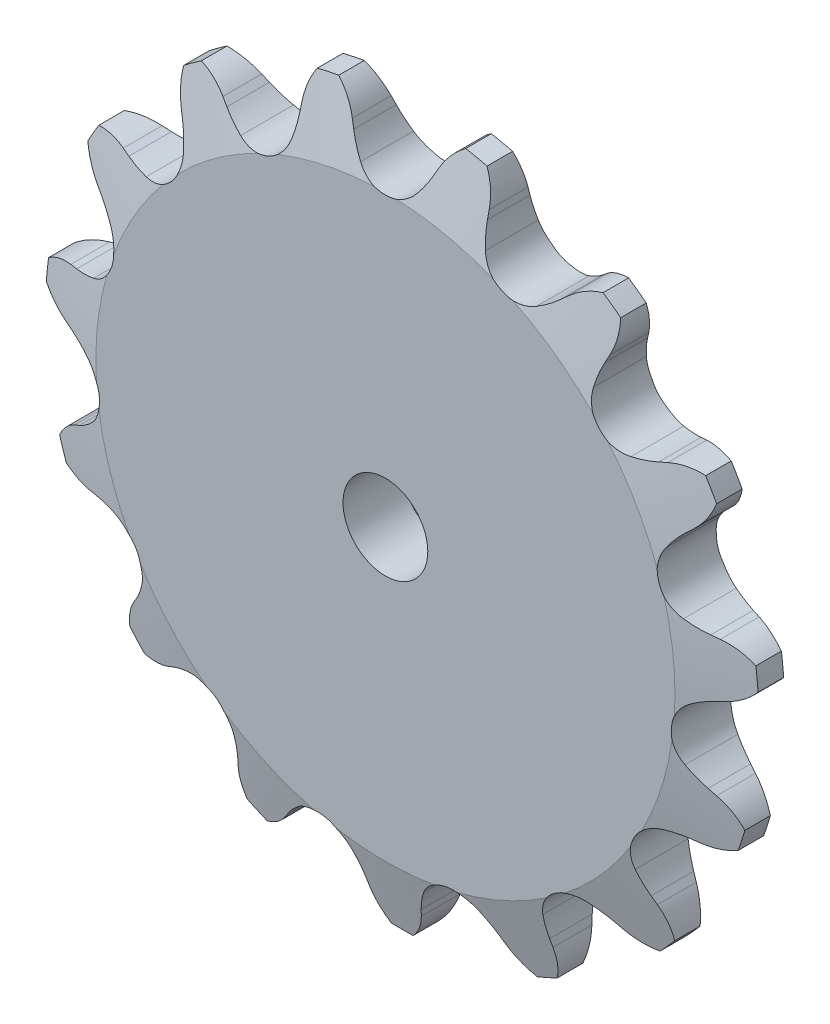
SolidWorks part; units mm, degrees
ref_plane "Front Plane" through (0, 0, 0) normal (0, 0, 1) x (1, 0, 0)
ref_plane "Top Plane" through (0, 0, 0) normal (0, 1, 0) x (1, 0, 0)
ref_plane "Right Plane" through (0, 0, 0) normal (1, 0, 0) x (0, 0, -1)
ref_axis "Axis1" through (0, 0, -88.99) along (0, 0, 1)
sketch "Sprocket-BaseSketch" plane through (0, 0, 0) normal (1, 0, 0) x (0, 0, -1)
  line L0 (1.397, 0) -> (1.397, 13.6672)
  line L1 (1.397, 13.6672) -> (0.6032, 16.8422)
  line L2 (0.6032, 16.8422) -> (-0.6032, 16.8422)
  line L3 (-0.6032, 16.8422) -> (-1.397, 13.6672)
  line L4 (-1.397, 13.6672) -> (-1.397, 0)
  line L5 (-1.397, 0) -> (1.397, 0)
  line L6 (5.588, 0) -> (-1.7463, 0) construction
  dimension "Hub Surface" = 1.397
  dimension "RightSide (1)" = 0.7938
  dimension "RightSide (2)" = 3.175
  dimension "OD" = 16.8422
  dimension "LeftSide (1)" = 0.7938
  dimension "LeftSide (2)" = 3.175
  dimension "Tooth Width" = 2.794
revolve "25 (04C) ANSI (ISO) Chain Number, 1.202in P.D." add sketch "Sprocket-BaseSketch" angle 360 about L6
sketch "Tooth-Sketch" plane through (0, 0, 0) normal (0, 0, 1) x (1, 0, 0)
  line L0 (0, 0) -> (0, 20.3612) construction
  line L1 (1.888, 15.1179) -> (2.042, 15.4521)
  line L2 (-1.888, 15.1179) -> (-2.042, 15.4521)
  line L3 (0, 15.2709) -> (6.2112, 13.9507) construction
  line L4 (0, 15.2709) -> (-6.2112, 13.9507) construction
  arc A0 (-1.3191, 14.2027) -> (1.3191, 14.2027) centre (0, 15.2709) ccw
  arc A1 (1.3191, 14.2027) -> (1.888, 15.1179) centre (-2.0529, 16.9333) ccw
  arc A2 (-1.3191, 14.2027) -> (-1.888, 15.1179) centre (2.0529, 16.9333) cw
  arc A3 (2.042, 15.4521) -> (4.5218, 17.0401) centre (4.5218, 14.3098) cw
  arc A4 (-2.042, 15.4521) -> (-4.5218, 17.0401) centre (-4.5218, 14.3098) ccw
  arc A5 (4.5218, 17.0401) -> (-4.5218, 17.0401) centre (0, 0) ccw
extrude "Tooth-Cut, Number of teeth: 15" cut sketch "Tooth-Sketch" against normal through all and the other way through all
pattern_circular "Tooth Pattern, 15 / 15" count 15 every 24 about axis through (0, 0, -88.99) along (0, 0, 1) of "Tooth-Cut, Number of teeth: 15"
sketch "Sketch4" plane through (0, 0, 0) normal (0, 0, 1) x (1, 0, 0)
  circle A0 centre (0, 0) radius 2
  dimension "D1" = 4
extrude "Cut-Extrude1" cut sketch "Sketch4" against normal through all and the other way through all
sketch "Sketch5" plane through (0, 0, 0) normal (0, 0, 1) x (1, 0, 0)
  circle A0 centre (0, 0) radius 16.8422
  dimension "D1" = 33.6844
equation "\"D1@Sketch5\" = \"OD@Sprocket-BaseSketch\"*2"
